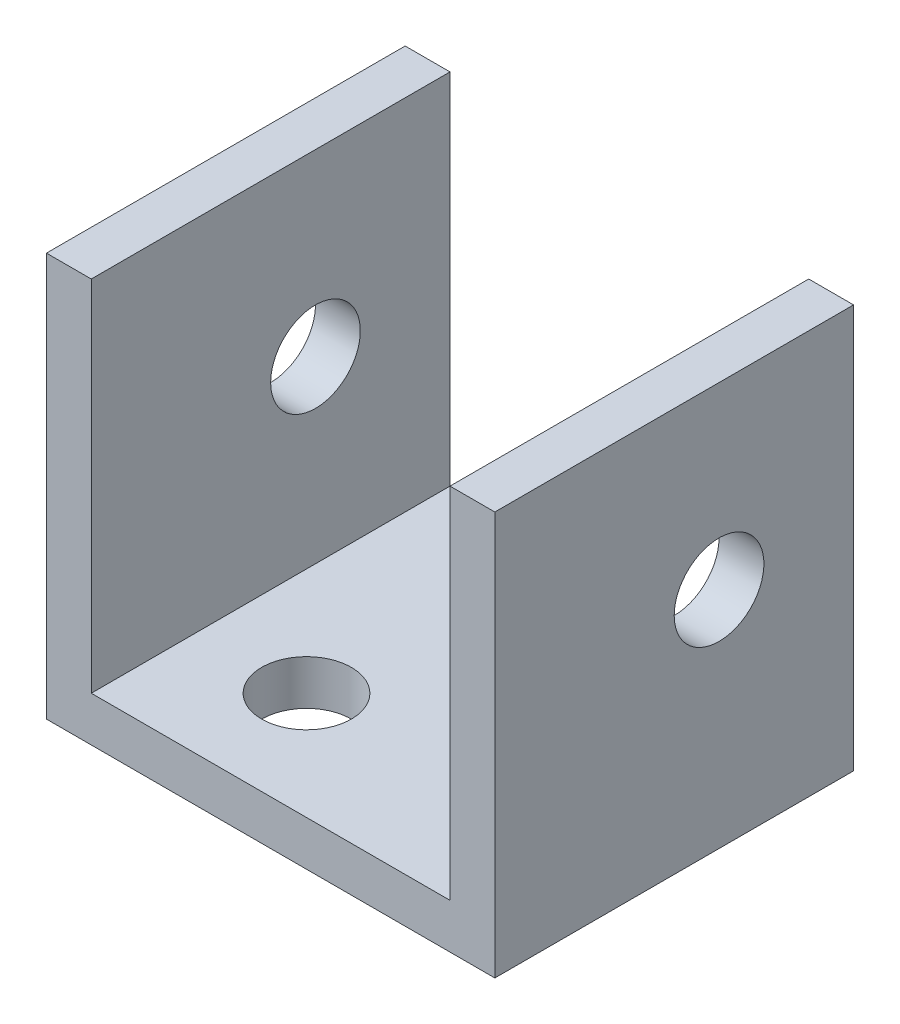
SolidWorks part; units mm, degrees
material "6061-T6 (SS)"
ref_plane "Front" through (0, 0, 0) normal (0, 0, 1) x (1, 0, 0)
ref_plane "Top" through (0, 0, 0) normal (0, 1, 0) x (1, 0, 0)
ref_plane "Right" through (0, 0, 0) normal (1, 0, 0) x (0, 0, -1)
sketch "Sketch1" plane through (0, 0, 0) normal (0, 1, 0) x (1, 0, 0)
  line L1 (-15.875, -12.7) -> (15.875, -12.7)
  line L2 (-15.875, -12.7) -> (-15.875, 12.7)
  line L3 (-15.875, 12.7) -> (15.875, 12.7)
  line L4 (15.875, -12.7) -> (15.875, 12.7)
  line L5 (-15.875, -12.7) -> (15.875, 12.7) construction
  line L6 (-15.875, 12.7) -> (15.875, -12.7) construction
  point P0 (0, 0)
  dimension "D1" = 31.75
  dimension "D2" = 25.4
extrude "Boss-Extrude1" add sketch "Sketch1" along normal blind 3.175
sketch "Sketch2" plane through (0, 3.175, 0) normal (0, 1, 0) x (1, 0, 0)
  line L0 (-15.875, 12.7) -> (-15.875, -12.7)
  line L1 (-15.875, -12.7) -> (-12.7, -12.7)
  line L2 (-15.875, -12.7) -> (15.875, -12.7) construction
  line L3 (-12.7, -12.7) -> (-12.7, 12.7)
  line L4 (15.875, 12.7) -> (-15.875, 12.7) construction
  line L5 (-12.7, 12.7) -> (-15.875, 12.7)
  line L6 (15.875, 12.7) -> (12.7, 12.7)
  line L7 (12.7, 12.7) -> (12.7, -12.7)
  line L8 (12.7, -12.7) -> (15.875, -12.7)
  line L9 (15.875, -12.7) -> (15.875, 12.7)
  point P13 (-8.7384, 15.875)
  point P17 (-1.1682, -15.875)
  point P18 (5.4674, -15.875)
  point P19 (-9.0656, -15.875)
  dimension "D1" = 3.175
extrude "Boss-Extrude2" add sketch "Sketch2" along normal blind 25.4
sketch "Sketch6" plane through (0, 3.175, 0) normal (0, 1, 0) x (1, 0, 0)
  line L0 (12.7, 12.7) -> (-12.7, 12.7) construction
  line L1 (12.7, 12.7) -> (12.7, -12.7) construction
  line L2 (-12.7, -12.7) -> (-12.7, 12.7) construction
  line L3 (-12.7, -12.7) -> (12.7, -12.7) construction
  point P0 (5.08, 5.08)
  point P2 (-5.08, -5.08)
  dimension "D1" = 7.62
  dimension "D2" = 7.62
  dimension "D3" = 7.62
  dimension "D4" = 7.62
hole_wizard "1/4 (0.25) Diameter Hole1" positions "Sketch6" profile "Sketch5" hole size "1/4" standard "ANSI Inch" end condition through all
sketch "Sketch5" plane through (5.08, 3.175, -5.08) normal (1, 0, 0) x (0, 0, 1)
  line L0 (0, 0) -> (0, 3.175)
  line L1 (0, 3.175) -> (3.175, 3.175)
  line L2 (3.175, 3.175) -> (3.175, 0)
  line L5 (3.175, 0) -> (0, 0)
  line L11 (0, -6.35) -> (0, 107.95) construction
  dimension "Thru Hole Dia." = 6.35
  dimension "Thru Hole Depth" = 3.175
sketch "Sketch9" plane through (-15.875, 0, 0) normal (-1, 0, 0) x (0, 0, 1)
  line L0 (-12.7, 28.575) -> (12.7, 28.575) construction
  line L1 (-12.7, 28.575) -> (-12.7, 0) construction
  point P0 (-3.175, 15.875)
  dimension "D1" = 12.7
  dimension "D2" = 9.525
hole_wizard "1/4 (0.25) Diameter Hole2" positions "Sketch9" profile "Sketch8" hole size "1/4" standard "ANSI Inch" end condition through all
sketch "Sketch8" plane through (-15.875, 15.875, -3.175) normal (0, 1, 0) x (0, 0, 1)
  line L0 (0, 0) -> (0, 31.75)
  line L1 (0, 31.75) -> (3.175, 31.75)
  line L2 (3.175, 31.75) -> (3.175, 0)
  line L5 (3.175, 0) -> (0, 0)
  line L11 (0, -6.35) -> (0, 107.95) construction
  dimension "Thru Hole Dia." = 6.35
  dimension "Thru Hole Depth" = 31.75
